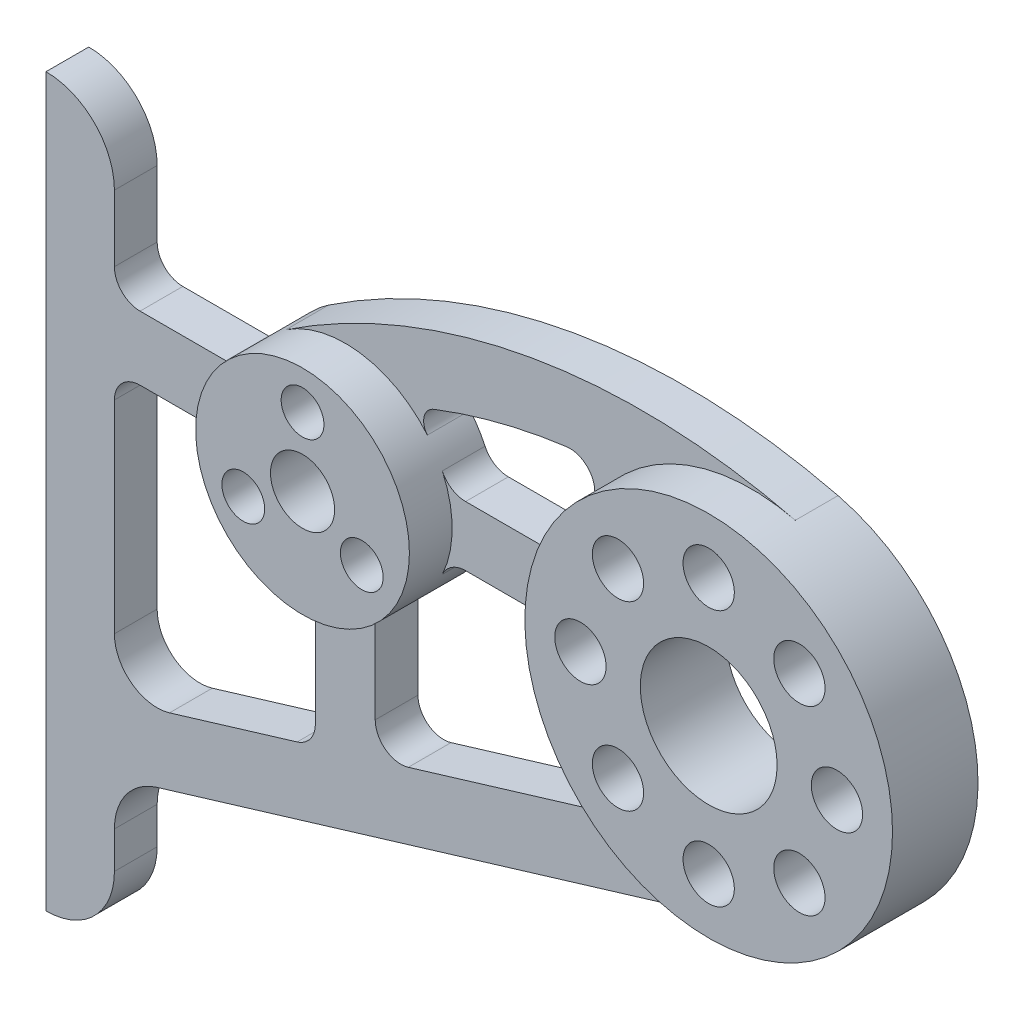
SolidWorks part; units mm, degrees
ref_plane "Спереди" through (0, 0, 0) normal (0, 0, 1) x (1, 0, 0)
ref_plane "Сверху" through (0, 0, 0) normal (0, 1, 0) x (1, 0, 0)
ref_plane "Справа" through (0, 0, 0) normal (1, 0, 0) x (0, 0, -1)
sketch "Эскиз1" plane through (0, 0, 0) normal (0, 0, 1) x (1, 0, 0)
  line L0 (0, 0) -> (0, 46.6588) construction
  line L1 (-70, 0) -> (184.2616, 0) construction
  line L2 (-70, 45) -> (-70, -125)
  line L3 (-54, 29) -> (-54, 13.5)
  line L4 (-48, 7.5) -> (-27.9061, 7.5)
  line L5 (-54, -100.3913) -> (-54, -109)
  line L6 (95, 61.6689) -> (95, -53.2616) construction
  line L7 (107.4511, -41.1579) -> (-44.0538, -86.9911)
  line L8 (-48, -7.5) -> (-27.9061, -7.5)
  line L9 (-54, -13.5) -> (-54, -60.8559)
  line L10 (-41.1044, -70.4275) -> (-11.2626, -61.3997)
  line L11 (-7, -55.6568) -> (-7, -28.1425)
  line L12 (7, -47.7913) -> (7, -28.1425)
  line L13 (14.7374, -53.5342) -> (55.3935, -41.235)
  line L14 (28.1425, 7) -> (47.756, 7)
  line L15 (28.1425, -7) -> (47.756, -7)
  line L16 (-54, -60.8559) -> (-54, -100.3913) construction
  line L17 (-44.0538, -86.9911) -> (-54, -90) construction
  circle A0 centre (0, 0) radius 7.5
  circle A1 centre (0, 16) radius 5
  circle A2 centre (13.8564, -8) radius 5
  circle A3 centre (-13.8564, -8) radius 5
  circle A4 centre (0, 0) radius 25
  arc A5 (-54, 13.5) -> (-48, 7.5) centre (-48, 13.5) ccw
  arc A6 (-27.9061, 7.5) -> (-22.5049, 10.8871) centre (-27.9061, 13.5) ccw
  arc A7 (-70, -125) -> (-54, -109) centre (-70, -109) ccw
  circle A8 centre (95, 0) radius 43
  circle A9 centre (95, 0) radius 16
  circle A10 centre (95, 30) radius 6
  circle A11 centre (116.2132, 21.2132) radius 6
  circle A12 centre (125, 0) radius 6
  circle A13 centre (116.2132, -21.2132) radius 6
  circle A14 centre (95, -30) radius 6
  circle A15 centre (73.7868, -21.2132) radius 6
  circle A16 centre (65, 0) radius 6
  circle A17 centre (73.7868, 21.2132) radius 6
  arc A18 (-13.8958, 20.7824) -> (105.2561, 41.759) centre (69.4789, -103.9119) cw
  arc A19 (-44.0538, -86.9911) -> (-54, -100.3913) centre (-40, -100.3913) ccw
  arc A20 (-27.9061, -7.5) -> (-22.5049, -10.8871) centre (-27.9061, -13.5) cw
  arc A21 (-54, -13.5) -> (-48, -7.5) centre (-48, -13.5) cw
  arc A22 (-54, -60.8559) -> (-41.1044, -70.4275) centre (-44, -60.8559) ccw
  arc A23 (14.7374, -53.5342) -> (7, -47.7913) centre (13, -47.7913) cw
  arc A24 (-7, -55.6568) -> (-11.2626, -61.3997) centre (-13, -55.6568) cw
  arc A25 (28.1425, -7) -> (22.6956, -10.4839) centre (28.1425, -13) ccw
  arc A26 (-7, -28.1425) -> (-10.4839, -22.6956) centre (-13, -28.1425) ccw
  arc A27 (55.3935, -41.235) -> (60.5171, -25.6891) centre (52.4979, -31.6634) ccw
  arc A28 (47.756, -7) -> (53.5409, -11.4082) centre (47.756, -13) cw
  arc A29 (7, -28.1425) -> (10.4839, -22.6956) centre (13, -28.1425) cw
  arc A30 (47.756, 7) -> (53.5409, 11.4082) centre (47.756, 13) ccw
  arc A31 (28.1425, 7) -> (22.6956, 10.4839) centre (28.1425, 13) cw
  arc A32 (20.7619, 21.9915) -> (19.2094, 16) centre (22.1368, 18.4383) ccw
  arc A33 (20.7619, 21.9915) -> (51.7272, 29.9159) centre (69.4789, -103.9119) cw
  arc A34 (51.7272, 29.9159) -> (57.5968, 21.2132) centre (52.4979, 24.105) cw
  arc A35 (-54, 29) -> (-70, 45) centre (-70, 29) ccw
  point P13 (0, 0)
  point P48 (95, 0)
  dimension "D1" = 15
  dimension "D2" = 10
  dimension "D5" = 50
  dimension "D9" = 6
  dimension "D10" = 16
  dimension "D11" = 16
  dimension "D12" = 86
  dimension "D14" = 32
  dimension "D15" = 12
  dimension "D18" = 150
  dimension "D19" = 90
  dimension "D21" = 15
  dimension "D20" = 6
  dimension "D22" = 10
  dimension "D23" = 6
  dimension "D24" = 6
  dimension "D25" = 10
  dimension "D27" = 6
  dimension "D28" = 6
  dimension "D30" = 6
  dimension "D32" = 135
  dimension "D37" = 6
  dimension "D36" = 14
  dimension "D3" = 16
  dimension "D6" = 70
  dimension "D7" = 45
  dimension "D8" = 170
  dimension "D13" = 95
  dimension "D16" = 30
  dimension "D26" = 14
  dimension "D29" = 14
  dimension "D34" = 15
  dimension "D35" = 16
  dimension "D4" = 3
  dimension "D17" = 8
extrude "Бобышка-Вытянуть1" add sketch "Эскиз1" along normal blind 10 contours A33 A34 A8 A18 A4 A32 | L14 A31 A4 A25 L15 A28 A8 A30 | L3 A35 L2 A7 L5 A19 L7 A8 A27 L13 A23 L12 A29 A4 A26 L11 A24 L10 A22 L9 A21 L8 A20 A6 L4 A5 region at (-60.4239, 38.5761, 0) region at (41.5567, 34.5362, 0) region at (38.5181, 0, 0)
extrude "Бобышка-Вытянуть2" add sketch "Эскиз1<3>" along normal blind 20 contours A4 A0 A1 A2 A3 | A8 A17 A16 A15 A14 A13 A12 A11 A10 A9 region at (81.9207, -39.684, 0) region at (-18.3274, 15.9453, 0)
sketch "Эскиз1<3>" plane through (0, 0, 0) normal (0, 0, 1) x (1, 0, 0) same geometry as "Эскиз1"
